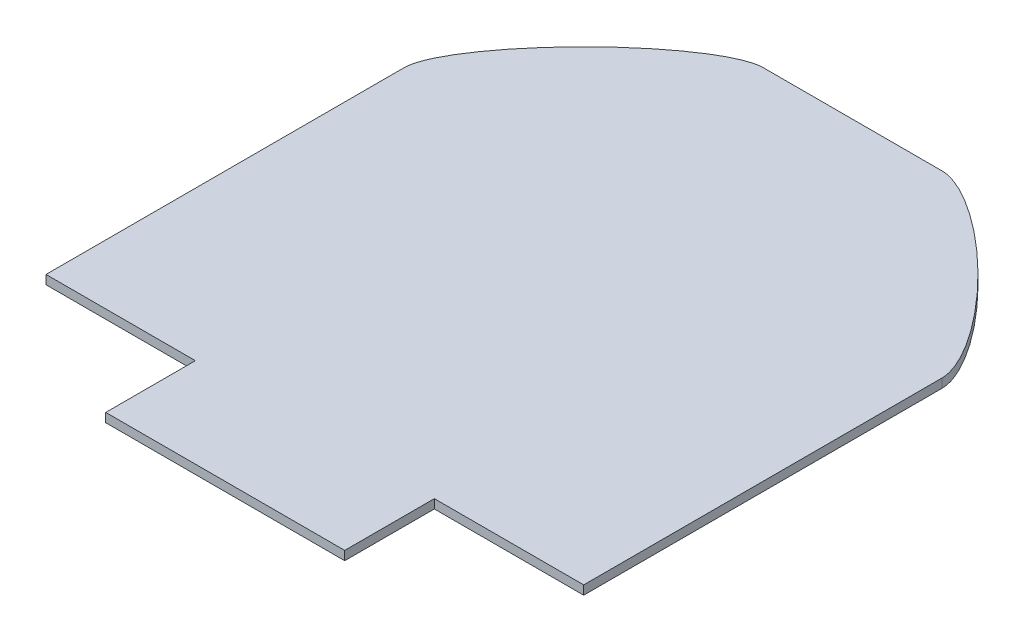
SolidWorks part; units mm, degrees
ref_plane "Front Plane" through (0, 0, 0) normal (0, 0, 1) x (1, 0, 0)
ref_plane "Top Plane" through (0, 0, 0) normal (0, 1, 0) x (1, 0, 0)
ref_plane "Right Plane" through (0, 0, 0) normal (1, 0, 0) x (0, 0, -1)
sketch "Sketch1" plane through (0, 0, 0) normal (0, 1, 0) x (1, 0, 0)
  line L0 (-90, 180) -> (-90, 0) construction
  line L1 (-180, 180) -> (0, 180)
  line L2 (-180, 180) -> (-180, 0)
  line L3 (-180, 0) -> (0, 0)
  line L4 (0, 180) -> (0, 0)
  line L5 (-180, 90) -> (0, 90) construction
  line L6 (-180, 30) -> (0, 30)
  line L7 (-130, 30) -> (-50, 30)
  line L8 (-130, 30) -> (-130, -30)
  line L9 (-130, -30) -> (-50, -30)
  line L10 (-50, 30) -> (-50, -30)
  line L11 (-130, 30) -> (-50, -30) construction
  line L12 (-130, -30) -> (-50, 30) construction
  dimension "D1" = 180
  dimension "D2" = 180
  dimension "D3" = 60
  dimension "D4" = 80
extrude "Boss-Extrude1" add sketch "Sketch1" along normal blind 3 contours L10 L3 L8 L9 | L2 L6 L4 L1 | L6 L10 L3 L4 | L8 L6 L2 L3 | L10 L6 L8 L3 region at (-90, 0, -105) region at (-155, 0, -15) region at (-25, 0, -15) region at (-90, 0, -15) region at (-90, 0, 15)
sketch "Sketch2" plane through (0, 3, 0) normal (0, 1, 0) x (1, 0, 0)
  line L0 (-180, 30) -> (0, 30)
  line L1 (-180, 180) -> (-180, 0) construction
  line L2 (0, 180) -> (0, 0) construction
  line L3 (-180, 180) -> (0, 180) construction
  line L4 (-90, 180) -> (-90, -30) construction
  line L5 (-130, -30) -> (-50, -30) construction
  dimension "D1" = 150
sketch "Sketch3" plane through (0, 3, 0) normal (0, 1, 0) x (1, 0, 0)
  line L0 (-180, 122) -> (0, 122)
  line L1 (-180, 180) -> (-180, 0) construction
  line L2 (0, 180) -> (0, 0) construction
  line L3 (-180, 30) -> (0, 30) construction
  dimension "D1" = 92
sketch "Sketch5" plane through (0, 3, 0) normal (0, 1, 0) x (1, 0, 0)
  line L0 (-114, 180) -> (-114, -30)
  line L1 (-180, 180) -> (0, 180) construction
  line L2 (-130, -30) -> (-50, -30) construction
  line L3 (-90, 180) -> (-90, -30) construction
  dimension "D1" = 24
fillet "Fillet1" radius 60 2 edges at (0, 1.5, -180) (-180, 1.5, -180) conic rho 0.2
